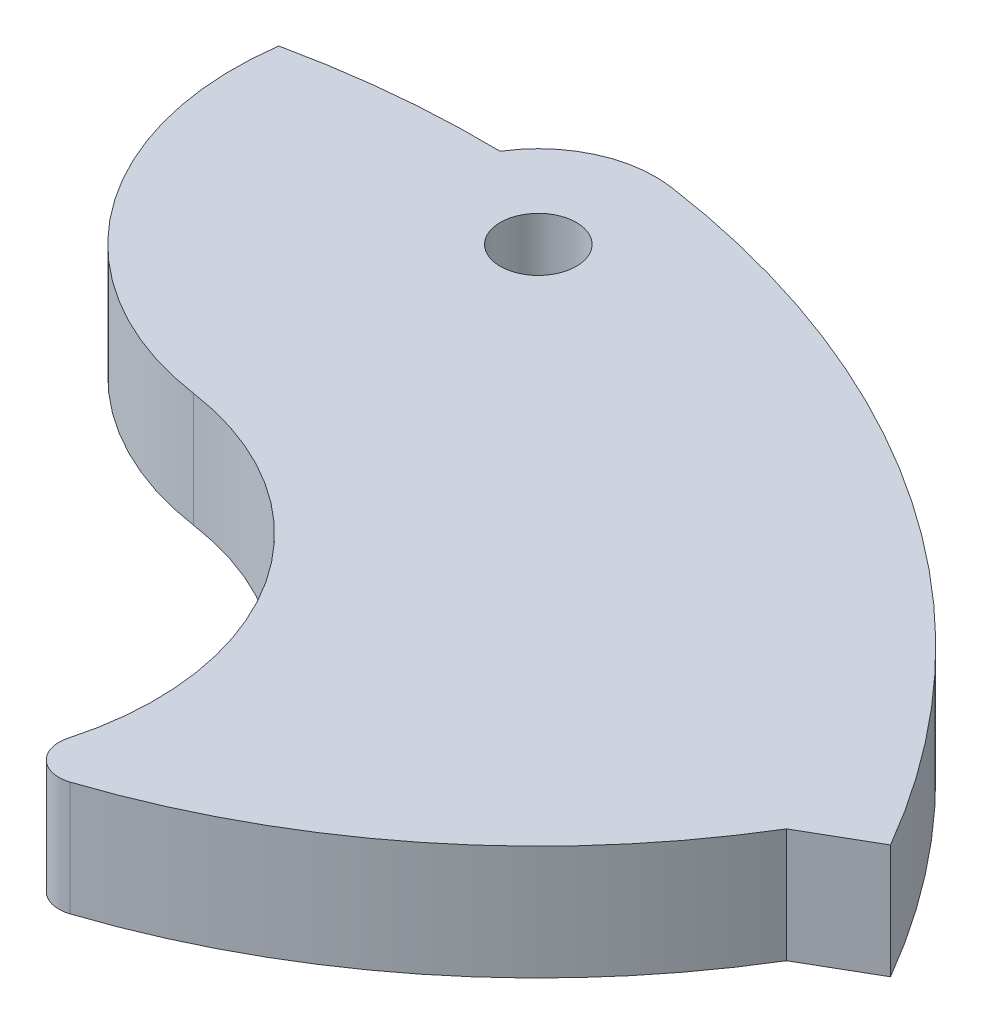
SolidWorks part; units mm, degrees
ref_plane "Front Plane" through (0, 0, 0) normal (0, 0, 1) x (1, 0, 0)
ref_plane "Top Plane" through (0, 0, 0) normal (0, 1, 0) x (1, 0, 0)
ref_plane "Right Plane" through (0, 0, 0) normal (1, 0, 0) x (0, 0, -1)
sketch "Sketch1" plane through (0, 0, 0) normal (0, 1, 0) x (1, 0, 0)
  line L2 (0, 97.8878) -> (0, 0) construction
  line L3 (0, 0) -> (88.0231, 50.8201) construction
  line L6 (67.8609, 39.1795) -> (62.3616, 36.0045)
  arc A1 (11.1734, 77.5583) -> (67.8609, 39.1795) centre (0, 0) cw
  circle A2 centre (9.779, 67.8792) radius 3.175
  circle A6 centre (0, 0) radius 25.4 construction
  arc A15 (62.3616, 36.0045) -> (29.0883, 9.5004) centre (9.779, 67.8792) cw
  arc A16 (11.1734, 77.5583) -> (1.4544, 73.0105) centre (9.779, 67.8792) ccw
  arc A17 (6.1571, 42.7388) -> (-15.3775, 71.3875) centre (9.779, 67.8792) cw
  circle A18 centre (4.8895, 33.9396) radius 8.89 construction
  arc A19 (6.1571, 42.7388) -> (25.8432, 12.5913) centre (2.7379, 19.0049) cw
  arc A20 (-15.3775, 71.3875) -> (1.4544, 73.0105) centre (0, 0) cw
  arc A21 (29.0883, 9.5004) -> (25.8432, 12.5913) centre (28.2907, 11.912) cw
  point P27 (24.0817, 8.0765)
  dimension "D1" = 78.359
  dimension "D4" = 6.35
  dimension "D8" = 50.8
  dimension "D9" = 25.4
  dimension "D11" = 17.78
  dimension "D7" = 73.025
  dimension "D10" = 2.54
  dimension "D5" = 68.58
  dimension "D2" = 72.009
  dimension "D6" = 60
  dimension "D3" = 9.779
  dimension "D12" = 34.29
extrude "Boss-Extrude1" add sketch "Sketch1" along normal blind 9.525
equation "\"AB_Coupler_OD_Length\"= 1in"
equation "\"AB_Coupling_Section_Length\"= 0.375in"
equation "\"AB_Coupler_Length\"= \"AB_Coupler_OD_Length\" + \"AB_Coupling_Section_Length\" * 2"
equation "\"AB_Coupler_Num_Screws\"= 6"
equation "\"Cutout_Angle\" = 60"
equation "\"AB_Coupling_Screw_Diameter\"= 0.1065in"
equation "\"Aft_Section_Length\"= 40in"
equation "\"Aft_Lower_Length\"= 20in"
equation "\"Aft_Upper_Length\"= \"Aft_Section_Length\" - \"Aft_Lower_Length\" - \"AB_Coupler_OD_Length\""
equation "\"Num_Cutouts\" = 4"
equation "\"Mid_Coupler_Length\" = 10in"
equation "\"Lead_Screw_Dist\" = 2.25in"
equation "\"Lead_Screw_Diam\" = (27/64)*1in"
equation "\"Lead_Screw_Length\" = (\"Mid_Coupler_Length\" + 2*0.375in + 2*0.5in)"
equation "\"Bodytube_OD\" = 6.17in"
equation "\"D1@Sketch1\"=\"Bodytube_OD\"/2"
equation "\"Paddle_Pin_Offset\" = \"Bodytube_OD\"/2-\"Paddle_Pin_Radius\""
equation "\"D5@Sketch1\"=2.7in"
equation "\"D2@Sketch1\"=\"Bodytube_OD\"/2-.25"
equation "\"D6@Sketch1\"=\"Cutout_Angle\""
equation "\"Paddle_Pin_Radius\" = 2.7in"
equation "\"AB_Coupler_OD\"= 6.17in"
equation "\"AB_Coupler_ID\"= 5.75in"
equation "\"AB_Coupler_Surface_Diameter\"= 5.998in"
equation "\"Bodytube_ID\" = 5.998in"
equation "\"D3@Sketch1\"=\"Paddle_Pin_Offset\""
equation "\"D7@Sketch1\"=\"AB_Coupler_ID\"/2"
